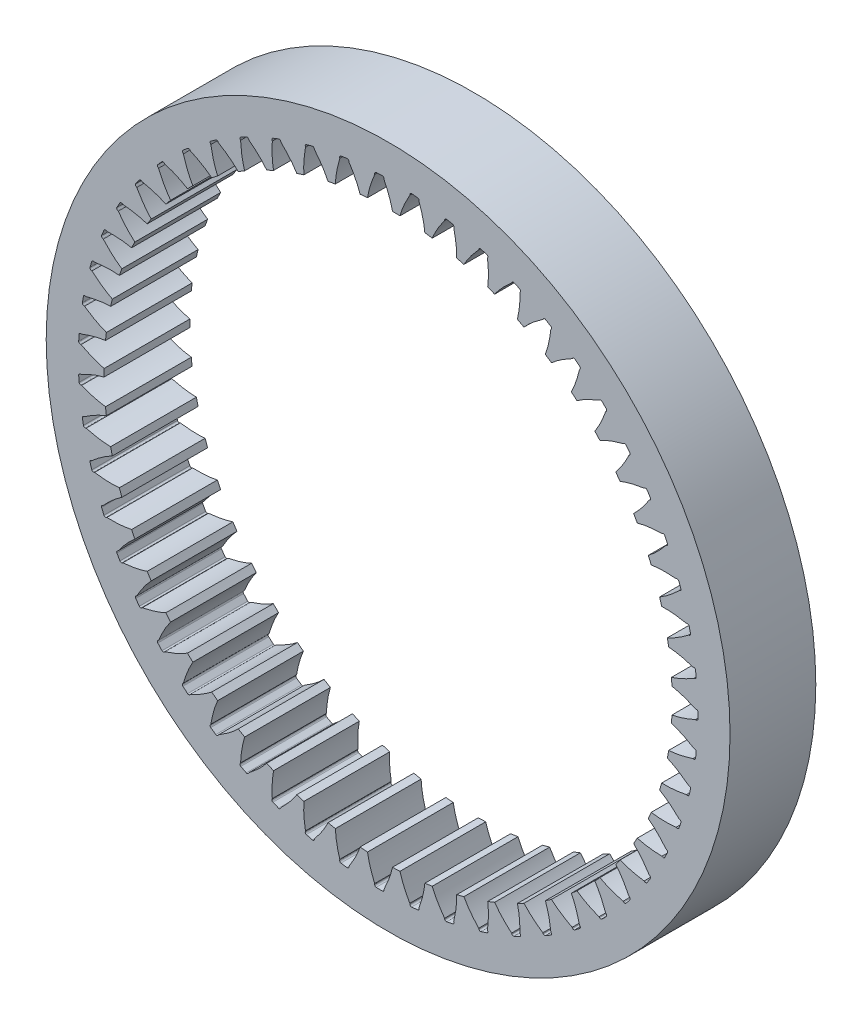
SolidWorks part; units mm, degrees
ref_plane "Front Plane" through (0, 0, 0) normal (0, 0, 1) x (1, 0, 0)
ref_plane "Top Plane" through (0, 0, 0) normal (0, 1, 0) x (1, 0, 0)
ref_plane "Right Plane" through (0, 0, 0) normal (1, 0, 0) x (0, 0, -1)
ref_axis "Gear Axis" through (0, 0, -0.5001) along (0, 0, 1)
sketch "Blank Sketch" plane through (0, 0, 0) normal (0, 0, 1) x (1, 0, 0)
  circle A0 centre (0, 0) radius 39.875
  circle A1 centre (0, 0) radius 33.125
  dimension "Rim" = 79.75
  dimension "Tip" = 66.25
extrude "Blank" add sketch "Blank Sketch" along normal blind 10
sketch "Tooth Space Sketch" plane through (0, 0, 0) normal (0, 0, 1) x (1, 0, 0)
  line L0 (32.4635, 1.5392) -> (31.8392, 1.5096)
  line L1 (32.4635, -1.5392) -> (31.8392, -1.5096)
  line L2 (31.8392, 1.5096) -> (31.8392, -1.5096)
  line L3 (35.8396, 0.5437) -> (35.9329, 0.5451)
  line L4 (35.8396, -0.5437) -> (35.9329, -0.5451)
  circle A0 centre (0, 0) radius 31.875 construction
  arc A1 (36.1232, 0.3595) -> (35.9329, 0.5451) centre (35.9357, 0.3576) ccw
  arc A2 (35.9329, -0.5451) -> (36.1232, -0.3595) centre (35.9357, -0.3576) ccw
  arc A3 (36.1232, -0.3595) -> (36.1232, 0.3595) centre (0, 0) ccw
  spline S0 degree 4 poles (32.3505, 1.5444) (32.3811, 1.5435) (32.4371, 1.541) (32.48, 1.5384) (32.5891, 1.5297) (32.672, 1.5209) (32.7778, 1.5084) (32.8834, 1.4932) (32.9935, 1.476) (33.1006, 1.4571) (33.209, 1.4366) (33.3161, 1.4146) (33.4235, 1.3912) (33.5537, 1.361) (33.7107, 1.322) (33.8922, 1.2735) (34.101, 1.2126) (34.3087, 1.1481) (34.5197, 1.0775) (34.7222, 1.0065) (34.935, 0.9266) (35.1275, 0.8521) (35.3502, 0.7598) (35.5193, 0.6886) (35.7615, 0.5799) (35.8715, 0.5293) (36.0233, 0.4575) (36.0999, 0.4205) (36.1389, 0.4015) (36.1587, 0.3918) knots 0 0 0 0 0 0.027604 0.045881 0.064918 0.092335 0.119753 0.14717 0.174587 0.202005 0.229422 0.256839 0.284256 0.311674 0.363255 0.418089 0.472924 0.527758 0.582593 0.637427 0.692262 0.747097 0.801931 0.856766 0.9116 0.9558 0.9779 1 1 1 1 1 construction
  spline S1 degree 4 poles (32.4635, 1.5392) (32.4797, 1.5381) (32.5126, 1.5358) (32.5891, 1.5297) (32.672, 1.5209) (32.7778, 1.5084) (32.8834, 1.4932) (32.9935, 1.476) (33.1006, 1.4571) (33.209, 1.4366) (33.3161, 1.4146) (33.4235, 1.3912) (33.5537, 1.361) (33.7107, 1.322) (33.8922, 1.2735) (34.101, 1.2126) (34.3087, 1.1481) (34.5197, 1.0775) (34.7222, 1.0065) (34.935, 0.9266) (35.1275, 0.8521) (35.3502, 0.7598) (35.5193, 0.6886) (35.7102, 0.603) (35.7956, 0.564) (35.8396, 0.5437) knots 0.027604 0.027604 0.027604 0.027604 0.027604 0.045881 0.064918 0.092335 0.119753 0.14717 0.174587 0.202005 0.229422 0.256839 0.284256 0.311674 0.363255 0.418089 0.472924 0.527758 0.582593 0.637427 0.692262 0.747097 0.801931 0.856766 0.9116 0.9116 0.9116 0.9116 0.9116
  spline S2 degree 4 poles (32.3505, -1.5444) (32.3811, -1.5435) (32.4371, -1.541) (32.48, -1.5384) (32.5891, -1.5297) (32.672, -1.5209) (32.7778, -1.5084) (32.8834, -1.4932) (32.9935, -1.476) (33.1006, -1.4571) (33.209, -1.4366) (33.3161, -1.4146) (33.4235, -1.3912) (33.5537, -1.361) (33.7107, -1.322) (33.8922, -1.2735) (34.101, -1.2126) (34.3087, -1.1481) (34.5197, -1.0775) (34.7222, -1.0065) (34.935, -0.9266) (35.1275, -0.8521) (35.3502, -0.7598) (35.5193, -0.6886) (35.7615, -0.5799) (35.8715, -0.5293) (36.0233, -0.4575) (36.0999, -0.4205) (36.1389, -0.4015) (36.1587, -0.3918) knots 0 0 0 0 0 0.027604 0.045881 0.064918 0.092335 0.119753 0.14717 0.174587 0.202005 0.229422 0.256839 0.284256 0.311674 0.363255 0.418089 0.472924 0.527758 0.582593 0.637427 0.692262 0.747097 0.801931 0.856766 0.9116 0.9558 0.9779 1 1 1 1 1 construction
  spline S3 degree 4 poles (32.4635, -1.5392) (32.4797, -1.5381) (32.5126, -1.5358) (32.5891, -1.5297) (32.672, -1.5209) (32.7778, -1.5084) (32.8834, -1.4932) (32.9935, -1.476) (33.1006, -1.4571) (33.209, -1.4366) (33.3161, -1.4146) (33.4235, -1.3912) (33.5537, -1.361) (33.7107, -1.322) (33.8922, -1.2735) (34.101, -1.2126) (34.3087, -1.1481) (34.5197, -1.0775) (34.7222, -1.0065) (34.935, -0.9266) (35.1275, -0.8521) (35.3502, -0.7598) (35.5193, -0.6886) (35.7102, -0.603) (35.7956, -0.564) (35.8396, -0.5437) knots 0.027604 0.027604 0.027604 0.027604 0.027604 0.045881 0.064918 0.092335 0.119753 0.14717 0.174587 0.202005 0.229422 0.256839 0.284256 0.311674 0.363255 0.418089 0.472924 0.527758 0.582593 0.637427 0.692262 0.747097 0.801931 0.856766 0.9116 0.9116 0.9116 0.9116 0.9116
  dimension "Root" = 36.125
  dimension "Fillet" = 0.1875
  dimension "Cap" = 63.75
extrude "Tooth Space" cut sketch "Tooth Space Sketch" against normal through all both and the other way through all both
pattern_circular "Teeth" count 55 over 360 about axis through (0, 0, -0.5001) along (0, 0, 1) of "Tooth Space"
equation "\"No. of Teeth\"= 55"
equation "\"Module\"= 1.25"
equation "\"Pressure Angle\"= 20"
equation "\"Inner Diameter\"= ( \"No. of Teeth\" - 2 ) * \"Module\""
equation "\"Pitch Diameter\"= \"No. of Teeth\" * \"Module\""
equation "\"Backlash\"= IIF ( \"Module\" <= 1 , 0.3 * \"Module\" , 0.3 )"
equation "\"Arc Length\"= ( ( \"Module\" * pi ) / 2 + \"Backlash\" )"
equation "\"Fillet Radius\"= 0.15 * \"Module\""
equation "\"Tooth Depth\"= IIF ( \"Module\" <= 1.25 , \"Module\" * 2.4 , \"Module\" * 2.25 )"
equation "\"Face Width\"= 10"
equation "\"Root Diameter\"= \"Inner Diameter\" + 2 * \"Tooth Depth\""
equation "\"Rim Diameter\"= \"Root Diameter\" + 6 * \"Module\""
equation "\"Base Diameter\"= \"Pitch Diameter\" * cos ( \"Pressure Angle\" )"
equation "\"Base Radius\"= \"Base Diameter\" / 2"
equation "\"Tooth Thickness\"= \"Module\" * pi - \"Arc Length\""
equation "\"Half Space Angle\"= ( \"Arc Length\" / \"Pitch Diameter\" ) * 180 / pi"
equation "\"Involute Fn\"= tan ( \"Pressure Angle\" ) - \"Pressure Angle\" * pi / 180"
equation "\"Flank Offset\"= 0 - \"Arc Length\" / \"Pitch Diameter\" - \"Involute Fn\""
equation "\"Tip Cap Diameter\"= \"Inner Diameter\" - 2 * \"Module\""
equation "\"Flank Start Diameter\"= IIF ( \"Base Diameter\" >= ( \"Inner Diameter\" - \"Module\" ) , \"Base Diameter\" , \"Inner Diameter\" - \"Module\" )"
equation "\"Flank End Diameter\"= \"Root Diameter\" - 3 * \"Fillet Radius\""
equation "\"Involute t1\"= ( abs ( ( \"Flank Start Diameter\" / \"Base Diameter\" ) ^ 2 - 1 ) ) ^ 0.5"
equation "\"Involute t2\"= ( abs ( ( \"Flank End Diameter\" / \"Base Diameter\" ) ^ 2 - 1 ) ) ^ 0.5"
equation "\"Flank Arc Radius\"= ( \"Pitch Diameter\" / 2 ) * sin ( \"Pressure Angle\" )"
equation "\"Flank Centre Angle\"= \"Half Space Angle\" - \"Pressure Angle\""
equation "\"Rim@Blank Sketch\"= \"Rim Diameter\""
equation "\"Tip@Blank Sketch\"= \"Inner Diameter\""
equation "\"Width@Blank\"= \"Face Width\""
equation "\"Root@Tooth Space Sketch\"= \"Root Diameter\" / 2"
equation "\"Fillet@Tooth Space Sketch\"= \"Fillet Radius\""
equation "\"Cap@Tooth Space Sketch\"= \"Tip Cap Diameter\""
equation "\"Count@Teeth\"= \"No. of Teeth\""
